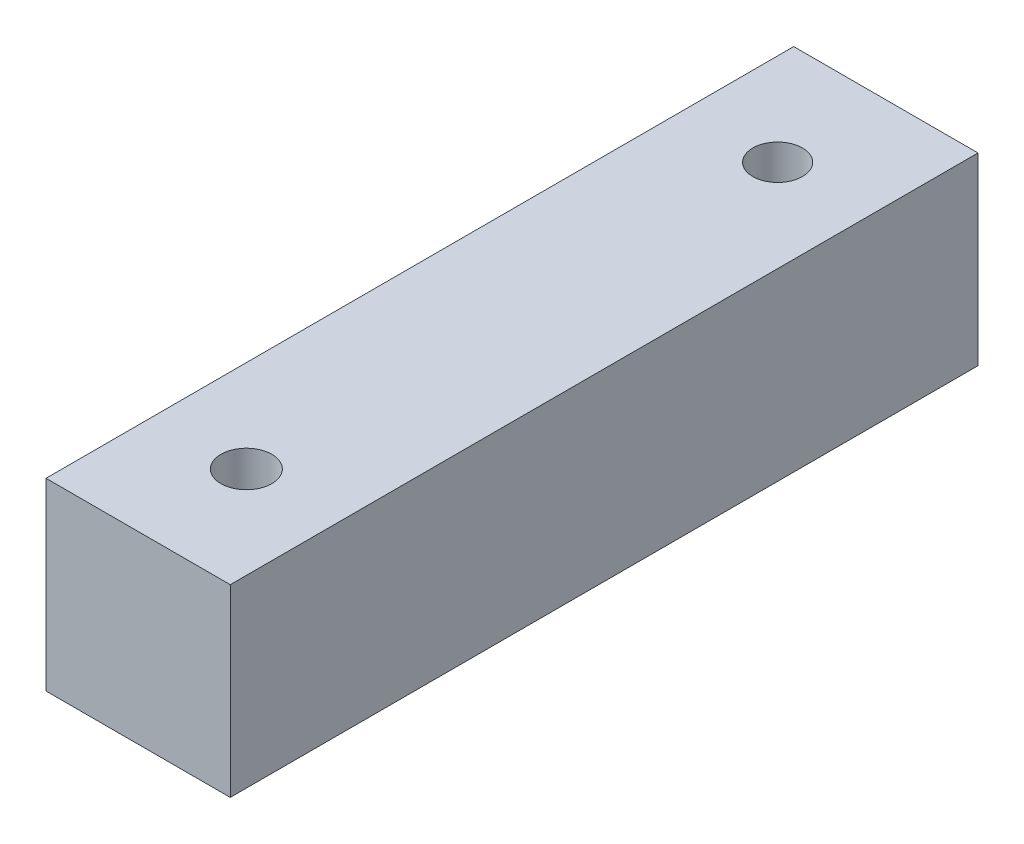
SolidWorks part; units mm, degrees
ref_plane "Front Plane" through (0, 0, 0) normal (0, 0, 1) x (1, 0, 0)
ref_plane "Top Plane" through (0, 0, 0) normal (0, 1, 0) x (1, 0, 0)
ref_plane "Right Plane" through (0, 0, 0) normal (1, 0, 0) x (0, 0, -1)
sketch "Sketch1" plane through (0, 0, 0) normal (0, 0, 1) x (1, 0, 0)
  line L1 (-6.35, -6.35) -> (6.35, -6.35)
  line L2 (-6.35, -6.35) -> (-6.35, 6.35)
  line L3 (-6.35, 6.35) -> (6.35, 6.35)
  line L4 (6.35, -6.35) -> (6.35, 6.35)
  line L5 (-6.35, -6.35) -> (6.35, 6.35) construction
  line L6 (-6.35, 6.35) -> (6.35, -6.35) construction
  point P0 (0, 0)
  dimension "D1" = 12.7
  dimension "D2" = 12.7
extrude "Boss-Extrude1" add sketch "Sketch1" along normal blind 51.5391
sketch "Sketch2" plane through (0, -6.35, 0) normal (0, -1, 0) x (1, 0, 0)
  circle A0 centre (0, 44.0779) radius 1.7545
  circle A1 centre (0, 7.4612) radius 1.7101
  dimension "D1" = 3.5091
  dimension "D2" = 3.4201
extrude "Cut-Extrude1" cut sketch "Sketch2" against normal through all
